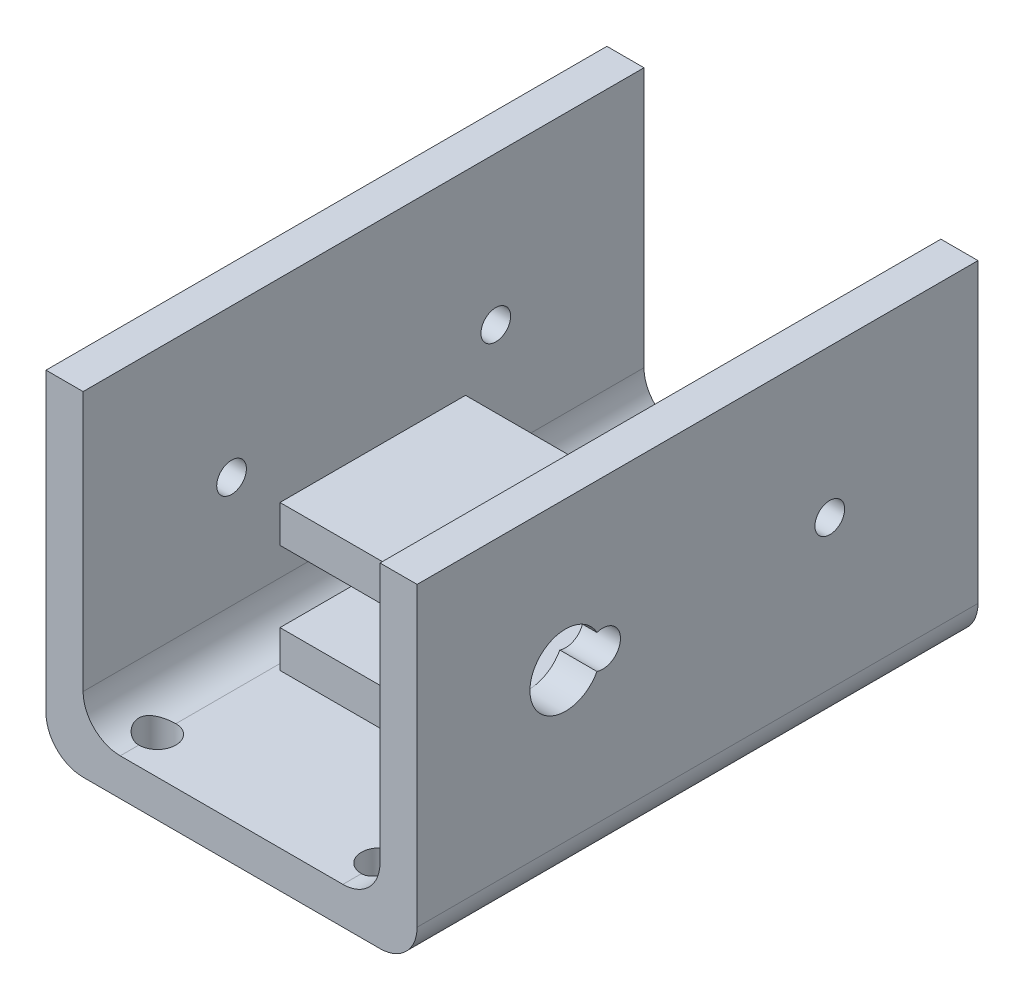
SolidWorks part; units mm, degrees
ref_plane "Front Plane" through (0, 0, 0) normal (0, 0, 1) x (1, 0, 0)
ref_plane "Top Plane" through (0, 0, 0) normal (0, 1, 0) x (1, 0, 0)
ref_plane "Right Plane" through (0, 0, 0) normal (1, 0, 0) x (0, 0, -1)
sketch "Sketch1" plane through (0, 0, 0) normal (0, 1, 0) x (1, 0, 0)
  line L0 (-25.4, -48.006) -> (-25.4, 47.9667)
  line L1 (-31.75, 47.9667) -> (31.75, 47.9667)
  line L2 (-31.75, 47.9667) -> (-31.75, -48.006)
  line L3 (-31.75, -48.006) -> (31.75, -48.006)
  line L4 (31.75, 47.9667) -> (31.75, -48.006)
  line L5 (25.4, 47.9667) -> (25.4, -48.006)
  circle A2 centre (0, 0) radius 3.81
  circle A3 centre (-19.05, -41.656) radius 3.175
  circle A4 centre (19.05, -41.656) radius 3.175
  circle A5 centre (-19.05, 41.6167) radius 3.175
  circle A6 centre (19.05, 41.6167) radius 3.175
  dimension "D7" = 7.62
  dimension "D8" = 6.35
  dimension "D9" = 6.35
  dimension "D10" = 6.35
  dimension "D11" = 6.35
  dimension "D1" = 31.75
  dimension "D2" = 63.5
  dimension "D3" = 48.006
  dimension "D4" = 95.9727
  dimension "D5" = 6.35
  dimension "D6" = 6.35
  dimension "D12" = 6.35
  dimension "D13" = 6.35
  dimension "D14" = 6.35
  dimension "D15" = 6.35
extrude "Boss-Extrude1" add sketch "Sketch1" along normal blind 6.35 contours L5 L1 L0 L3 A3 A2 region at (-24.3141, 0, 0.0197)
extrude "Boss-Extrude2" add sketch "Sketch1<3>" along normal blind 57.15 contours L2 L3 L0 L1 | L1 L5 L3 L4 region at (-28.575, 0, 0.0197) region at (28.575, 0, 0.0197)
sketch "Sketch1<3>" plane through (0, 0, 0) normal (0, 1, 0) x (1, 0, 0) same geometry as "Sketch1"
fillet "Fillet1" radius 6.35 4 edges at (25.4, 6.35, 0.0197) (-25.4, 6.35, 0.0197) (-31.75, 0, 0.0197) (31.75, 0, 0.0197)
sketch "Sketch2" plane through (31.75, 0, 0) normal (1, 0, 0) x (0, 0, -1)
  line L0 (-48.006, 6.35) -> (47.9667, 6.35) construction
  line L1 (47.9667, 57.15) -> (-48.006, 57.15) construction
  line L3 (-48.006, 57.15) -> (-48.006, 6.35) construction
  circle A0 centre (-22.606, 31.75) radius 6.096
  circle A1 centre (22.606, 31.75) radius 2.54
  circle A2 centre (-22.606, 31.75) radius 2.54
  circle A3 centre (-16.256, 31.75) radius 3.048
  dimension "D1" = 12.192
  dimension "D2" = 5.08
  dimension "D7" = 5.08
  dimension "D8" = 6.096
  dimension "D3" = 25.4
  dimension "D4" = 45.212
  dimension "D5" = 25.4
  dimension "D6" = 25.4
  dimension "D9" = 6.35
  dimension "D10" = 25.4
extrude "Cut-Extrude1" cut sketch "Sketch2" against normal up to surface (6.35 mm away) contours A2 | A0 A2 | A0 A3 | A0 A3 region at (31.75, 31.75, 17.8119) region at (31.75, 31.75, 15.2368) region at (31.75, 31.75, 19.4714) region at (31.75, 31.75, 22.606) up to face at (25.4, 34.925, 0.0197)
extrude "Cut-Extrude2" cut sketch "Sketch2<4>" against normal up to surface (63.5 mm away) contours A2 | A1 up to face at (-31.75, 31.75, 0.0197)
sketch "Sketch2<4>" plane through (31.75, 0, 0) normal (1, 0, 0) x (0, 0, -1) same geometry as "Sketch2"
sketch "Sketch3" plane through (25.4, 0, 0) normal (-1, 0, 0) x (0, 0, 1)
  line L1 (34.6419, 19.304) -> (2.8919, 19.304)
  line L2 (34.6419, 19.304) -> (34.6419, 25.654)
  line L3 (34.6419, 25.654) -> (2.8919, 25.654)
  line L4 (2.8919, 19.304) -> (2.8919, 25.654)
  line L6 (34.6419, 37.846) -> (2.8919, 37.846)
  line L7 (34.6419, 37.846) -> (34.6419, 44.196)
  line L8 (34.6419, 44.196) -> (2.8919, 44.196)
  line L9 (2.8919, 37.846) -> (2.8919, 44.196)
  circle A0 centre (22.606, 31.75) radius 6.096 construction
  dimension "D3" = 6.096
  dimension "D4" = 6.096
  dimension "D1" = 6.35
  dimension "D2" = 6.35
  dimension "D7" = 31.75
extrude "Boss-Extrude4" add sketch "Sketch3" along normal blind 30.48
